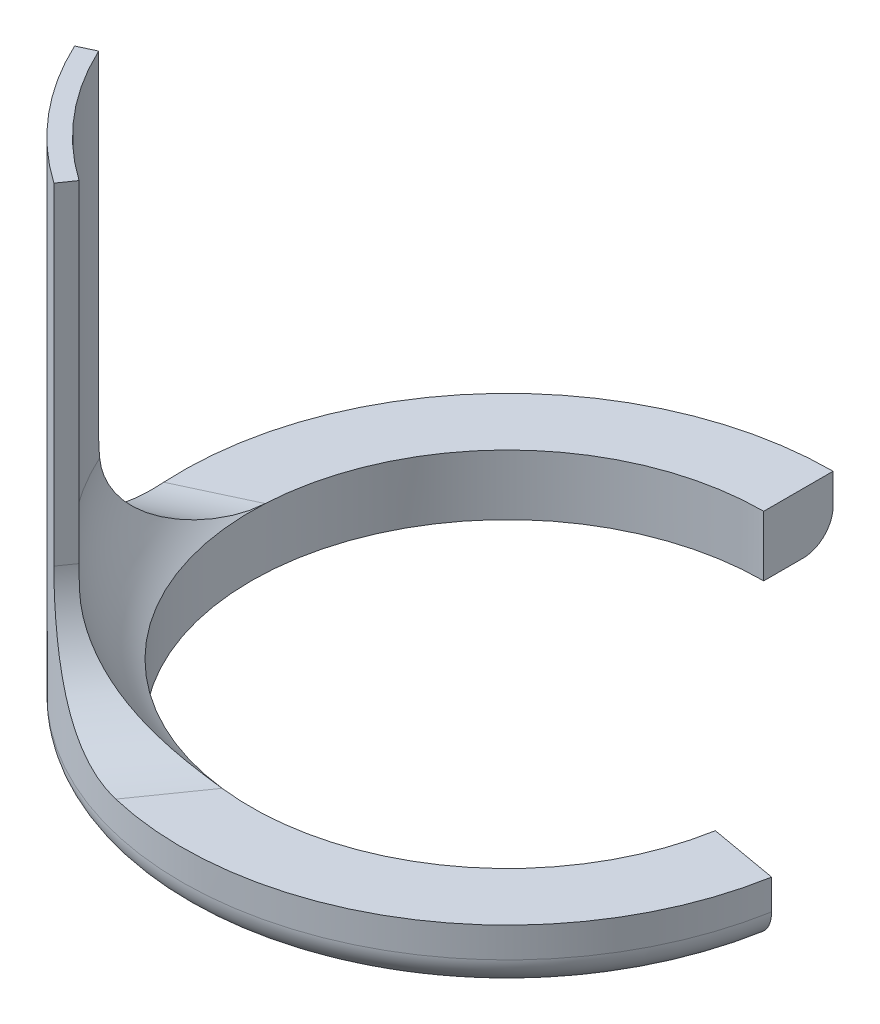
SolidWorks part; units mm, degrees
ref_plane "Front Plane" through (0, 0, 0) normal (0, 0, 1) x (1, 0, 0)
ref_plane "Top Plane" through (0, 0, 0) normal (0, 1, 0) x (1, 0, 0)
ref_plane "Right Plane" through (0, 0, 0) normal (1, 0, 0) x (0, 0, -1)
sketch "Sketch1" plane through (0, 0, 0) normal (0, 1, 0) x (1, 0, 0)
  line L0 (0, 13.716) -> (0, 0)
  line L1 (0, 0) -> (13.5076, -2.3818)
  circle A0 centre (0, 0) radius 10.795
  circle A1 centre (0, 0) radius 13.716
  dimension "D1" = 21.59
  dimension "D2" = 27.432
  dimension "D3" = 100
extrude "Boss-Extrude1" add sketch "Sketch1" along normal blind 2.54 contours L0 A1 L1 A0
sketch "Sketch2" plane through (0, 2.54, 0) normal (0, 1, 0) x (1, 0, 0)
  line L0 (10.631, -1.8745) -> (0, 10.795) construction
  line L1 (5.3155, 4.4602) -> (-10.5071, -8.8165) construction
  line L2 (0, 0) -> (-7.8672, -11.2355)
  line L3 (0, 0) -> (-12.4309, -5.7966)
  arc A0 (0, 13.716) -> (13.5076, -2.3818) centre (0, 0) ccw construction
  circle A1 centre (0, 0) radius 13.716
  circle A2 centre (0, 0) radius 12.954
  arc M4 (0, 13.716) -> (13.5076, -2.3818) centre (0, 0) ccw
  dimension "D2" = 0.762
  dimension "D1" = 15
extrude "Boss-Extrude2" add sketch "Sketch2" along normal blind 19.05 contours A2 L3 L2 M4
fillet "Fillet5" radius 5.08 3 edges at (-9.9233, 2.54, 8.3267) (-7.6486, 2.54, 10.9234) (-12.0856, 2.54, 5.6356)
fillet "Fillet6" radius 1.27 1 edges at (-10.5071, 0, 8.8165)
